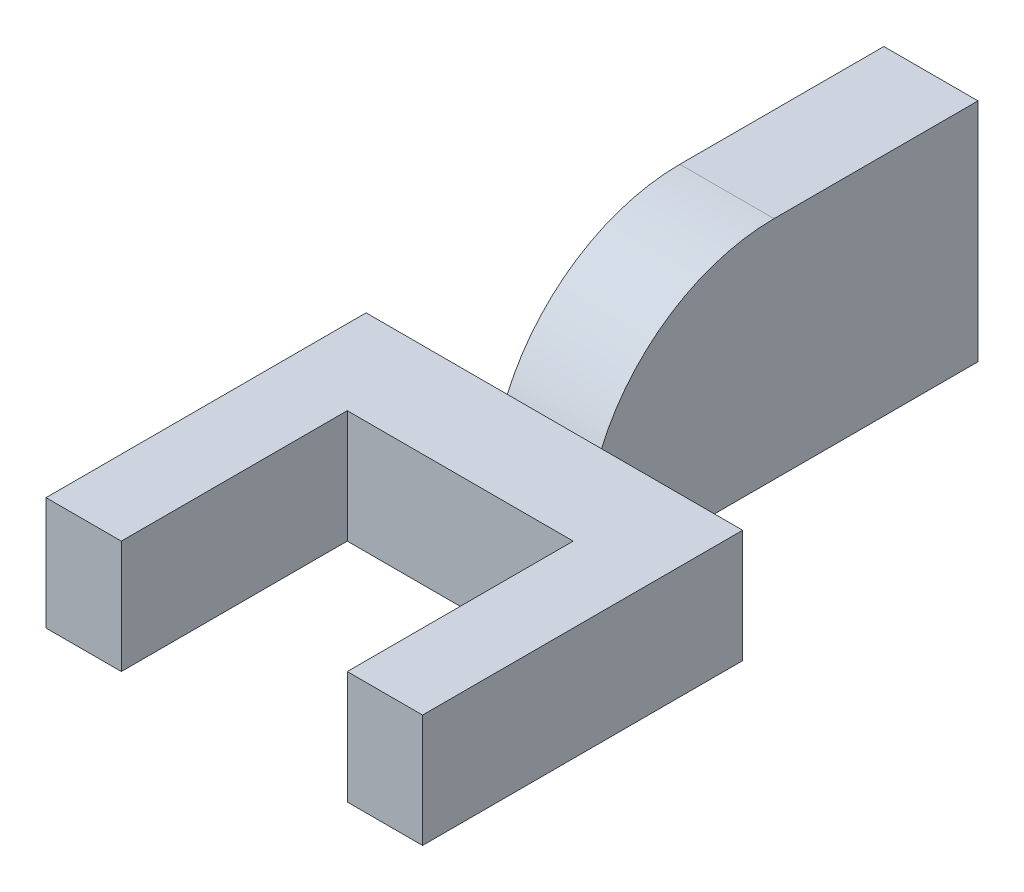
SolidWorks part; units mm, degrees
ref_plane "Front Plane" through (0, 0, 0) normal (0, 0, 1) x (1, 0, 0)
ref_plane "Top Plane" through (0, 0, 0) normal (0, 1, 0) x (1, 0, 0)
ref_plane "Right Plane" through (0, 0, 0) normal (1, 0, 0) x (0, 0, -1)
sketch "Sketch2" plane through (0, 0, 0) normal (0, 1, 0) x (1, 0, 0)
  line L1 (-6, 11.25) -> (6, 11.25)
  line L2 (-6, 11.25) -> (-6, -11.25)
  line L3 (-6, -11.25) -> (6, -11.25)
  line L4 (6, 11.25) -> (6, -11.25)
  line L5 (-6, 11.25) -> (6, -11.25) construction
  line L6 (-6, -11.25) -> (6, 11.25) construction
  line L7 (-10, 16.25) -> (10, 16.25)
  line L8 (-10, 16.25) -> (-10, -0.75)
  line L9 (-10, -0.75) -> (10, -0.75)
  line L10 (10, 16.25) -> (10, -0.75)
  line L11 (-10, 16.25) -> (10, -0.75) construction
  line L12 (-10, -0.75) -> (10, 16.25) construction
  point P0 (0, 0)
  point P6 (0, 7.75)
  point P11 (0, 0)
  point P12 (9.4531, 14.4805)
  point P13 (9.0939, 0)
  dimension "D1" = 22.5
  dimension "D2" = 12
  dimension "D3" = 5
  dimension "D4" = 17
  dimension "D5" = 20
extrude "Boss-Extrude1" add sketch "Sketch2" along normal blind 12 contours L10 L7 L8 L9 L2 L1 L4 region at (-6.2625, 0, -5.25)
sketch "Sketch3" plane through (0, 12, 0) normal (0, 1, 0) x (1, 0, 0)
  line L0 (-10, 16.25) -> (10, 16.25) construction
  line L1 (-2.5, 36.25) -> (2.5, 36.25)
  line L2 (-2.5, 36.25) -> (-2.5, 16.25)
  line L3 (-2.5, 16.25) -> (2.5, 16.25)
  line L4 (2.5, 36.25) -> (2.5, 16.25)
  line L5 (-2.5, 36.25) -> (2.5, 16.25) construction
  line L6 (-2.5, 16.25) -> (2.5, 36.25) construction
  point P0 (0, 26.25)
  point P7 (0, 0)
  dimension "D1" = 5
  dimension "D2" = 20
extrude "Boss-Extrude2" add sketch "Sketch3" against normal blind 12
sketch "Sketch4" plane through (10, 0, 0) normal (1, 0, 0) x (0, 0, -1)
  line L0 (16.25, 12) -> (16.25, 0) construction
  line L1 (-0.75, 12) -> (16.25, 12)
  line L2 (-0.75, 12) -> (-0.75, 6)
  line L3 (-0.75, 6) -> (16.25, 6)
  line L4 (16.25, 12) -> (16.25, 6)
extrude "Cut-Extrude1" cut sketch "Sketch4" against normal through all both and the other way through all
fillet "Fillet1" radius 10 1 edges at (0, 12, -16.25)
